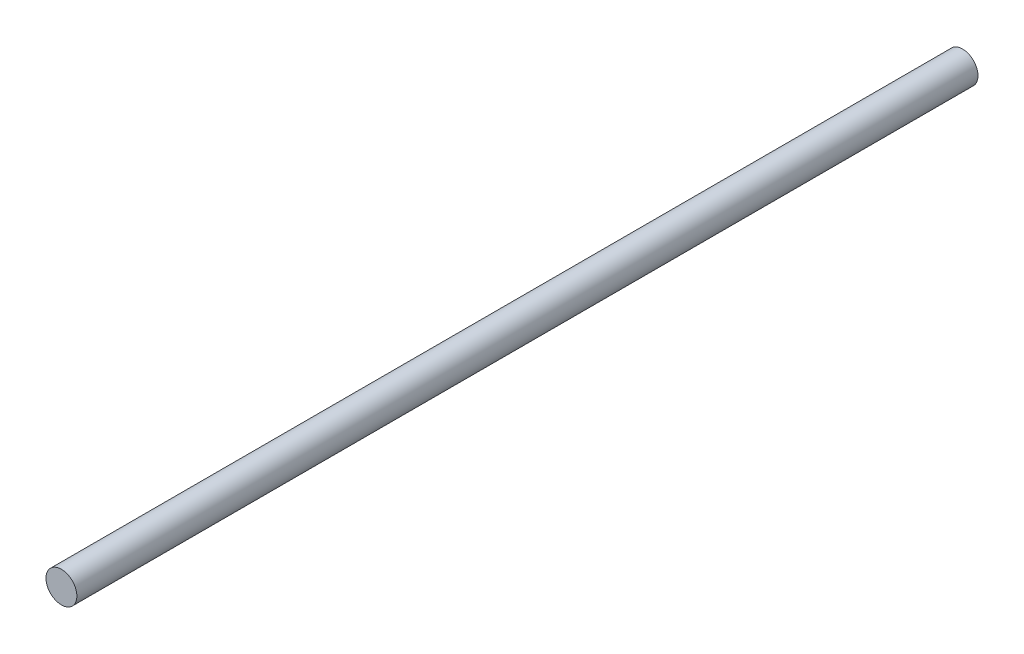
SolidWorks part; units mm, degrees
material "Plain Carbon Steel"
ref_plane "Front Plane" through (0, 0, 0) normal (0, 0, 1) x (1, 0, 0)
ref_plane "Top Plane" through (0, 0, 0) normal (0, 1, 0) x (1, 0, 0)
ref_plane "Right Plane" through (0, 0, 0) normal (1, 0, 0) x (0, 0, -1)
sketch "Sketch1" plane through (0, 0, 0) normal (0, 0, 1) x (1, 0, 0)
  circle A0 centre (0, 0) radius 6
  dimension "D1" = 12
extrude "Boss-Extrude1" add sketch "Sketch1" along normal blind 350
sketch "Sketch2" plane through (0, 0, 0) normal (0, 0, -1) x (-1, 0, 0)
  line L1 (4.2864, 6.0867) -> (9.6874, 6.0867)
  line L2 (4.2864, 6.0867) -> (4.2864, -6.3439)
  line L3 (4.2864, -6.3439) -> (9.6874, -6.3439)
  line L4 (9.6874, 6.0867) -> (9.6874, -6.3439)
extrude "Cut-Extrude1" [suppressed] cut sketch "Sketch2" against normal blind 24 from offset 100 offset against normal yes
ref_plane "Plane1" through (0, 0, 175) normal (0, 0, 1) x (1, 0, 0)
mirror "Mirror1" [suppressed] about plane through (0, 0, 175) normal (0, 0, 1)
